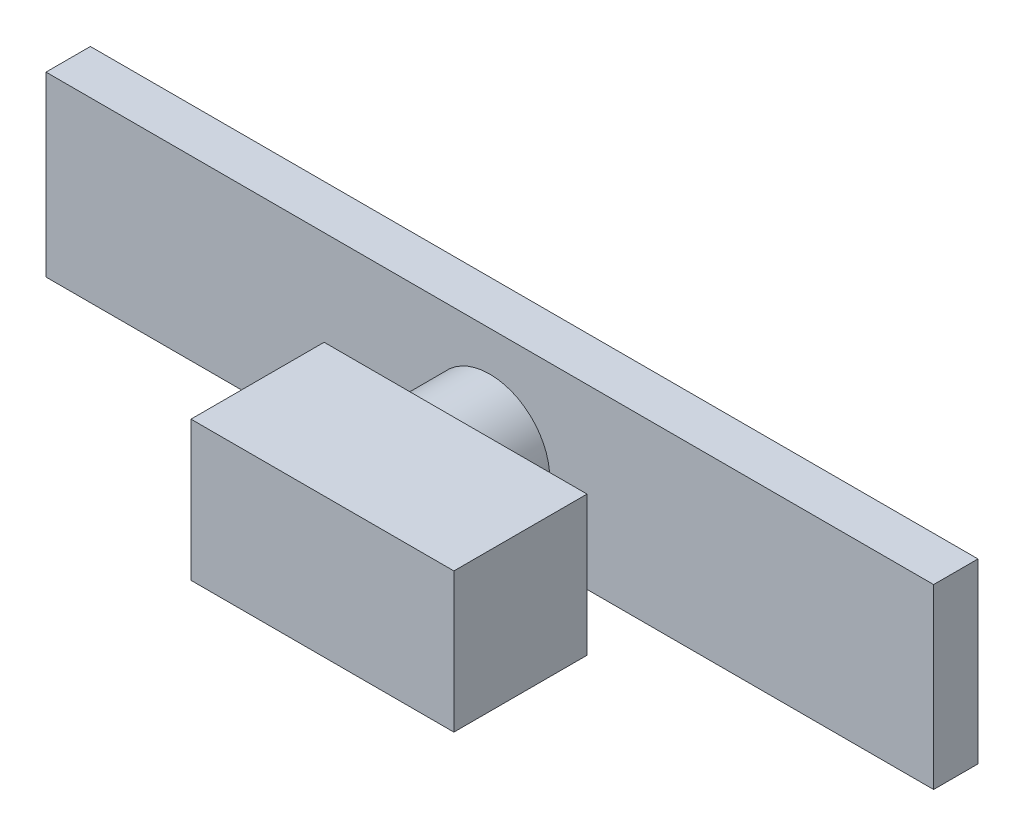
SolidWorks part; units mm, degrees
ref_plane "Front Plane" through (0, 0, 0) normal (0, 0, 1) x (1, 0, 0)
ref_plane "Top Plane" through (0, 0, 0) normal (0, 1, 0) x (1, 0, 0)
ref_plane "Right Plane" through (0, 0, 0) normal (1, 0, 0) x (0, 0, -1)
sketch "Sketch2" plane through (0, 0, 0) normal (0, 0, 1) x (1, 0, 0)
  line L1 (-47.8692, 21.2481) -> (206.1308, 21.2481)
  line L2 (-47.8692, 21.2481) -> (-47.8692, 8.5481)
  line L3 (-47.8692, 8.5481) -> (206.1308, 8.5481)
  line L4 (206.1308, 21.2481) -> (206.1308, 8.5481)
  dimension "D1" = 12.7
  dimension "D2" = 254
extrude "Boss-Extrude1" add sketch "Sketch2" along normal blind 50.8
sketch "Sketch3" plane through (0, 21.2481, 0) normal (0, 1, 0) x (1, 0, 0)
  circle A0 centre (79.1308, -28.4831) radius 17.1408
extrude "Boss-Extrude2" add sketch "Sketch3" along normal blind 19.05
sketch "Sketch4" plane through (0, 40.2981, 0) normal (0, 1, 0) x (1, 0, 0)
  line L1 (50.7675, -8.111) -> (126.0034, -8.111)
  line L2 (50.7675, -8.111) -> (50.7675, -48.0661)
  line L3 (50.7675, -48.0661) -> (126.0034, -48.0661)
  line L4 (126.0034, -8.111) -> (126.0034, -48.0661)
extrude "Boss-Extrude3" add sketch "Sketch4" along normal blind 38.1
scale "Scale2" scale about centroid uniform scaling yes scale factor 0.06
move or copy body "rotate" bodies to move or copy 105 copy no rotation origin (0, 33.6669, 26.5501) rotation axis (1, 0, 0) rotation angle 90
scale "Scale5" scale about centroid uniform scaling yes scale factor 0.25
move or copy body "-4 x" bodies to move or copy 111 copy no translate (-101.6, 0, 0)
move or copy body "-2 y" bodies to move or copy 117 copy no translate (0, -55.88, 0)
scale "Scale6" bodies to scale 121 scale about centroid uniform scaling yes scale factor 0.25
move or copy body "-2.1z" bodies to move or copy 122 copy no translate (0, 0, -30.48)
